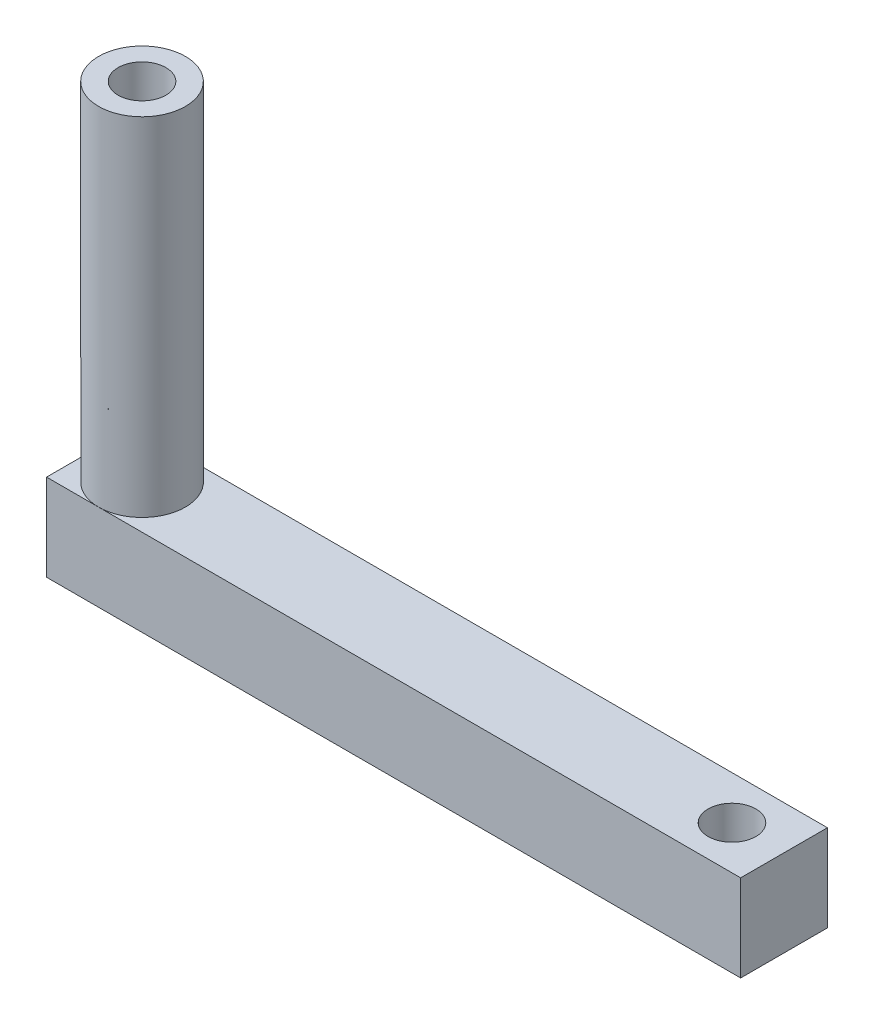
SolidWorks part; units mm, degrees
ref_plane "Front Plane" through (0, 0, 0) normal (0, 0, 1) x (1, 0, 0)
ref_plane "Top Plane" through (0, 0, 0) normal (0, 1, 0) x (1, 0, 0)
ref_plane "Right Plane" through (0, 0, 0) normal (1, 0, 0) x (0, 0, -1)
sketch "Sketch1" plane through (0, 0, 0) normal (0, 1, 0) x (1, 0, 0)
  line L1 (0, 0) -> (50.8, 0)
  line L2 (0, 0) -> (0, 6.35)
  line L3 (0, 6.35) -> (50.8, 6.35)
  line L4 (50.8, 0) -> (50.8, 6.35)
  circle A0 centre (3.81, 3.175) radius 1.75
  circle A1 centre (46.99, 3.175) radius 1.75
  point P9 (3.81, 3.1728)
  dimension "D1" = 3.5
  dimension "D2" = 43.18
  dimension "D3" = 3.81
  dimension "D4" = 3.81
  dimension "D5" = 6.35
  dimension "D6" = 3.175
extrude "Boss-Extrude1" add sketch "Sketch1" against normal blind 6.35
sketch "Sketch2" plane through (0, -6.35, 0) normal (0, -1, 0) x (1, 0, 0)
  line L1 (0, 0) -> (50.8, 0) construction
  circle A0 centre (3.81, -3.175) radius 3.175
  circle A1 centre (3.81, -3.175) radius 1.75
  circle A2 centre (3.81, -3.175) radius 1.75 construction
extrude "Boss-Extrude2" add sketch "Sketch2" against normal blind 25.4 from offset 6.35 offset against normal yes
